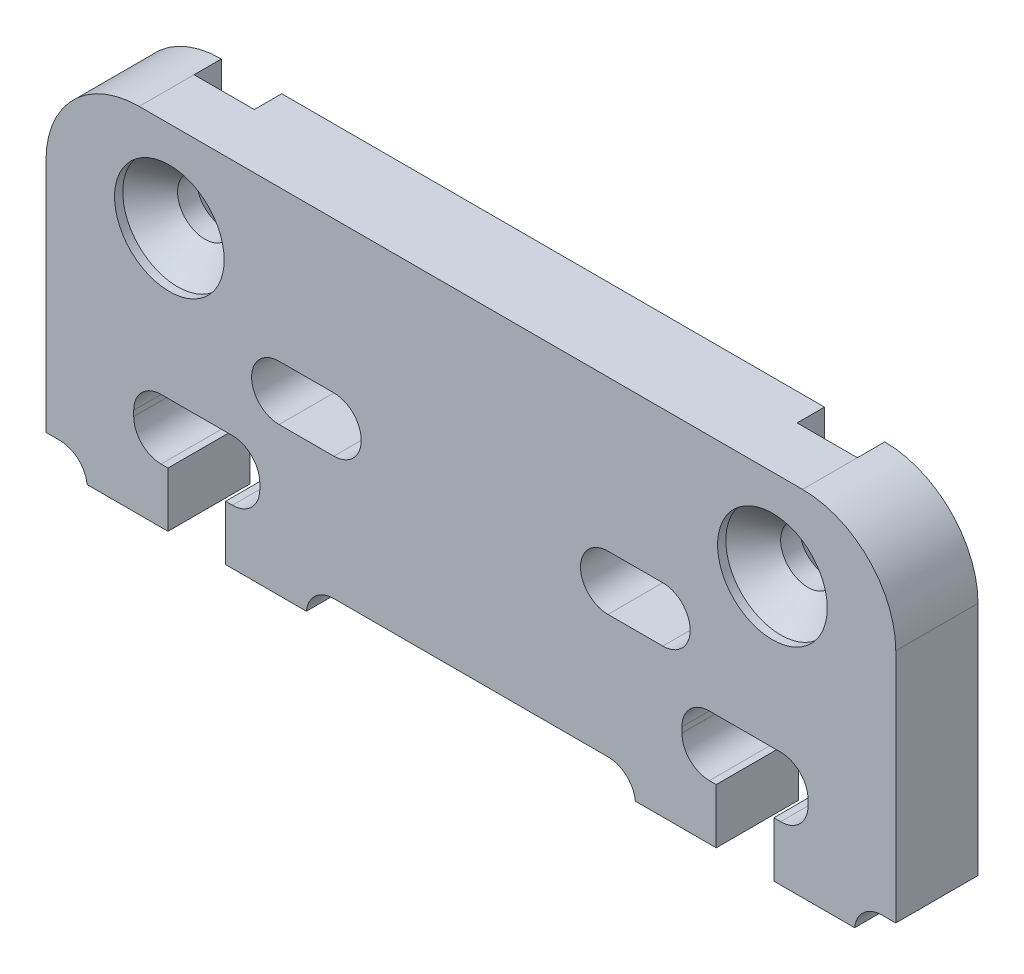
SolidWorks part; units mm, degrees
ref_plane "Front Plane" through (0, 0, 0) normal (0, 0, 1) x (1, 0, 0)
ref_plane "Top Plane" through (0, 0, 0) normal (0, 1, 0) x (1, 0, 0)
ref_plane "Right Plane" through (0, 0, 0) normal (1, 0, 0) x (0, 0, -1)
sketch "Sketch1" plane through (0, 0, 0) normal (0, 0, 1) x (1, 0, 0)
  line L0 (-10, -6.9) -> (-10, 6) construction
  line L1 (-15.5, 6) -> (15.5, 6)
  line L2 (-15.5, 6) -> (-15.5, -6)
  line L3 (-15.5, -6) -> (15.5, -6)
  line L4 (15.5, 6) -> (15.5, -6)
  line L5 (-15.5, 6) -> (15.5, -6) construction
  line L6 (-15.5, -6) -> (15.5, 6) construction
  line L7 (-15.5, -6) -> (-6, -6)
  line L9 (-14, -6.9) -> (-6, -6.9)
  line L10 (-6, -6) -> (-6, -6.9)
  line L11 (0, 6) -> (0, -6) construction
  line L12 (-11.05, -4.9) -> (-8.95, -4.9)
  line L13 (-11.05, -4.9) -> (-11.05, -6.9)
  line L14 (-11.05, -6.9) -> (-8.95, -6.9)
  line L15 (-8.95, -4.9) -> (-8.95, -6.9)
  line L16 (-11.05, -4.9) -> (-8.95, -6.9) construction
  line L17 (-11.05, -6.9) -> (-8.95, -4.9) construction
  line L18 (-12.3, -2.7) -> (-7.7, -2.7)
  line L19 (-12.3, -2.7) -> (-12.3, -4.9)
  line L20 (-12.3, -4.9) -> (-7.7, -4.9)
  line L21 (-7.7, -2.7) -> (-7.7, -4.9)
  line L22 (-12.3, -2.7) -> (-7.7, -4.9) construction
  line L23 (-12.3, -4.9) -> (-7.7, -2.7) construction
  line L24 (12.3, -2.7) -> (7.7, -2.7)
  line L25 (12.3, -2.7) -> (12.3, -4.9)
  line L26 (12.3, -4.9) -> (7.7, -4.9)
  line L27 (7.7, -2.7) -> (7.7, -4.9)
  line L28 (11.05, -4.9) -> (8.95, -4.9)
  line L29 (11.05, -4.9) -> (11.05, -6.9)
  line L30 (11.05, -6.9) -> (8.95, -6.9)
  line L31 (8.95, -4.9) -> (8.95, -6.9)
  line L32 (15.5, -6) -> (6, -6)
  line L33 (6, -6) -> (6, -6.9)
  line L34 (14, -6.9) -> (6, -6.9)
  line L36 (-14, -6.9) -> (-14, -6)
  line L37 (14, -6.9) -> (14, -6)
  line L38 (10, -2.7) -> (10, -6.9) construction
  line L39 (7, -0.5) -> (5, -0.5) construction
  line L40 (7, -1.5) -> (5, -1.5)
  line L41 (7, 0.5) -> (5, 0.5)
  line L42 (-7, -0.5) -> (-5, -0.5) construction
  line L43 (-7, -1.5) -> (-5, -1.5)
  line L44 (-7, 0.5) -> (-5, 0.5)
  arc A0 (7, -1.5) -> (7, 0.5) centre (7, -0.5) ccw
  arc A1 (5, 0.5) -> (5, -1.5) centre (5, -0.5) ccw
  arc A2 (-7, -1.5) -> (-7, 0.5) centre (-7, -0.5) cw
  arc A3 (-5, 0.5) -> (-5, -1.5) centre (-5, -0.5) cw
  point P0 (0, 0)
  point P11 (-10, -5.9)
  point P16 (-10, -3.8)
  point P40 (6, -0.5)
  point P47 (-6, -0.5)
  dimension "D1" = 31
  dimension "D2" = 12
  dimension "D3" = 0.9
  dimension "D4" = 8
  dimension "D5" = 2.1
  dimension "D6" = 2
  dimension "D7" = 2.2
  dimension "D8" = 4.6
  dimension "D9" = 20
  dimension "D10" = 2
  dimension "D11" = 2
  dimension "D12" = 12
  dimension "D13" = 5.5
extrude "Base shape" add sketch "Sketch1" along normal blind 3 contours L31 L26 L27 L24 L25 L29 L3 L4 L1 L2 L13 L20 L19 L18 L21 L15 | L3 L15 L9 L10 | L13 L3 L9 | L34 L31 L3 L33 | L3 L29 L34 region at (0, 0.3282, 0) region at (-12.525, -6.45, 0) region at (12.525, -6.45, 0) region at (-7.475, -6.45, 0) region at (7.475, -6.45, 0)
fillet "Edge radiuses" radius 3.4 2 edges at (15.5, 6, 1.5) (-15.5, 6, 1.5)
sketch "Sketch2" plane through (0, 0, 0) normal (0, 0, -1) x (-1, 0, 0)
  line L0 (0, 6) -> (0, -6) construction
  line L10 (12.1, 6) -> (-12.1, 6) construction
  line L11 (6, -6) -> (-6, -6) construction
  line L16 (-14, -6) -> (-15.5, -6) construction
  line L17 (-12.1, 6.1) -> (-9.9, 6.1)
  line L18 (-12.1, 6.1) -> (-12.1, 0.3)
  line L19 (-11.1, -0.7) -> (-10.9, -0.7)
  line L20 (-9.9, 6.1) -> (-9.9, 0.3)
  line L21 (-12.1, 6.1) -> (-9.9, -0.7) construction
  line L22 (-12.1, -0.7) -> (-9.9, 6.1) construction
  line L23 (12.1, 6.1) -> (9.9, 6.1)
  line L24 (12.1, 6.1) -> (12.1, 0.3)
  line L25 (11.1, -0.7) -> (10.9, -0.7)
  line L26 (9.9, 6.1) -> (9.9, 0.3)
  arc A8 (-10.9, -0.7) -> (-9.9, 0.3) centre (-10.9, 0.3) ccw
  arc A9 (-12.1, 0.3) -> (-11.1, -0.7) centre (-11.1, 0.3) ccw
  arc A10 (12.1, 0.3) -> (11.1, -0.7) centre (11.1, 0.3) cw
  arc A11 (10.9, -0.7) -> (9.9, 0.3) centre (10.9, 0.3) cw
  point P6 (-11, 2.7)
  dimension "D5" = 1
  dimension "D1" = 6.8
  dimension "D2" = 2.2
  dimension "D3" = 22
  dimension "D4" = 8.7
extrude "Camera mount pockets" cut sketch "Sketch2" against normal blind 1
sketch "Sketch3" plane through (0, 0, 1) normal (0, 0, -1) x (-1, 0, 0)
  line L3 (0, 6) -> (0, -6) construction
  line L5 (6, -6) -> (-6, -6) construction
  line L6 (-11.1, -0.7) -> (-10.9, -0.7) construction
  line L7 (-12.1, 6.1) -> (-9.9, 6.1)
  line L8 (-12.1, 6.1) -> (-12.1, -0.7)
  line L9 (-12.1, -0.7) -> (-9.9, -0.7)
  line L10 (-9.9, 6.1) -> (-9.9, -0.7)
  line L11 (-12.1, 6.1) -> (-9.9, -0.7) construction
  line L12 (-12.1, -0.7) -> (-9.9, 6.1) construction
  line L13 (-12.1, 6) -> (-12.1, 0.3) construction
  circle A0 centre (-11, 2.7) radius 1
  circle A1 centre (11, 2.7) radius 1
  point P2 (-11, 2.7)
  point P17 (-11, -0.7)
  point P18 (-11, -0.7)
  dimension "D1" = 2
  dimension "D2" = 6.8
extrude "Camera mount holes" cut sketch "Sketch3" against normal up to next contours A0 | A1 region at (11, 2.7, 1) region at (-11, 2.7, 1)
hole_wizard "CSK for M2 Flat Head Machine Screw1" positions "Sketch4" profile "Sketch5" countersink size "M2" standard "ANSI Metric" end condition through all
sketch "Sketch4" plane through (0, 0, 3) normal (0, 0, 1) x (1, 0, 0)
  point P0 (-11, 2.7)
  point P3 (11, 2.7)
sketch "Sketch5" plane through (-11, 2.7, 3) normal (1, 0, 0) x (0, -1, 0)
  line L0 (0, 0) -> (0, 3)
  line L1 (0, 3) -> (1, 3)
  line L2 (1, 3) -> (1, 1.3)
  line L3 (1, 1.3) -> (2, 0.3)
  line L4 (2, 0.3) -> (2, 0)
  line L6 (2, 0) -> (0, 0)
  line L7 (-1, 1.3) -> (-2, 0.3) construction
  line L11 (0, -6.35) -> (0, 107.95) construction
  dimension "Thru Hole Dia." = 2
  dimension "Thru Hole Depth" = 3
  dimension "C'Sink Dia." = 4
  dimension "C'Sink Angle" = 90
  dimension "Head Clearance" = 0.3
fillet "1mm milling radiuses" radius 1 12 edges at (-7.7, -2.7, 1.5) (-7.7, -4.9, 1.5) (12.3, -4.9, 1.5) (12.3, -2.7, 1.5) (7.7, -2.7, 1.5) (7.7, -4.9, 1.5) (-12.3, -4.9, 1.5) (-12.3, -2.7, 1.5) (14, -6, 1.5) (6, -6, 1.5) (-14, -6, 1.5) (-6, -6, 1.5)
sketch "Slot sketch" plane through (0, 0, 1) normal (0, 0, -1) x (-1, 0, 0)
  line L0 (0, 6) -> (0, -6) construction
  line L3 (-12.1, 7.2) -> (-9.9, 7.2)
  line L4 (-12.1, 6) -> (-12.1, 0.3)
  line L5 (-11.1, -0.7) -> (-10.9, -0.7)
  line L6 (-9.9, 0.3) -> (-9.9, 6)
  line L7 (-9.9, 6) -> (-12.1, 6)
  line L9 (-11.1, -0.7) -> (-10.9, -0.7)
  line L12 (9.9, 6) -> (-9.9, 6) construction
  line L25 (-12.1, 0.3) -> (-12.1, 7.2)
  line L26 (-9.9, 0.3) -> (-9.9, 7.2)
  line L27 (11.1, -0.7) -> (10.9, -0.7)
  line L28 (12.1, 0.3) -> (12.1, 7.2)
  line L29 (12.1, 7.2) -> (9.9, 7.2)
  line L30 (9.9, 0.3) -> (9.9, 7.2)
  line L31 (5.005, -6) -> (-5.005, -6) construction
  arc A2 (-12.1, 0.3) -> (-11.1, -0.7) centre (-11.1, 0.3) ccw
  arc A3 (-10.9, -0.7) -> (-9.9, 0.3) centre (-10.9, 0.3) ccw
  arc A4 (-12.1, 0.3) -> (-11.1, -0.7) centre (-11.1, 0.3) ccw
  arc A5 (-10.9, -0.7) -> (-9.9, 0.3) centre (-10.9, 0.3) ccw
  arc A6 (10.9, -0.7) -> (9.9, 0.3) centre (10.9, 0.3) cw
  arc A7 (12.1, 0.3) -> (11.1, -0.7) centre (11.1, 0.3) cw
  point P13 (0, 0)
  point P14 (0, 0)
  dimension "D3" = 1.2
  dimension "D1" = 0
